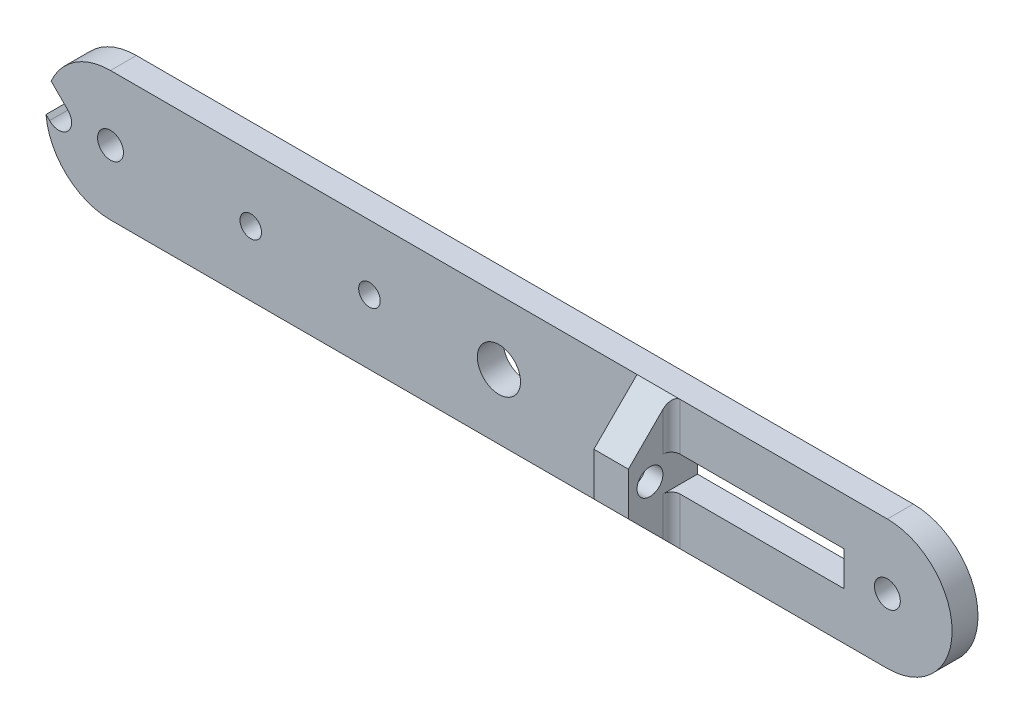
SolidWorks part; units mm, degrees
ref_plane "Plan de face" through (0, 0, 0) normal (0, 0, 1) x (1, 0, 0)
ref_plane "Plan de dessus" through (0, 0, 0) normal (0, 1, 0) x (1, 0, 0)
ref_plane "Plan de droite" through (0, 0, 0) normal (1, 0, 0) x (0, 0, -1)
sketch "Esquisse1" plane through (0, 0, 0) normal (0, 0, 1) x (1, 0, 0)
  line L0 (-74.3787, 0) -> (69.7437, 0) construction
  line L1 (0, 0) -> (0, 19.0596) construction
  line L2 (90, -15) -> (-90, -15)
  line L3 (90, 15) -> (-90, 15)
  line L5 (40, -4) -> (80, -4)
  line L6 (40, -4) -> (40, 4)
  line L7 (40, 4) -> (80, 4)
  line L8 (80, -4) -> (80, 4)
  line L9 (40, -4) -> (80, 4) construction
  line L10 (40, 4) -> (80, -4) construction
  arc A0 (90, -15) -> (90, 15) centre (90, 0) ccw
  circle A1 centre (90, 0) radius 3
  circle A2 centre (-90, 0) radius 3
  arc A3 (-90, -15) -> (-90, 15) centre (-90, 0) cw
  circle A4 centre (0, 0) radius 5
  circle A5 centre (-57.5, 0) radius 2.5
  circle A6 centre (-30, 0) radius 2.5
  point P4 (60, 0)
  point P17 (0, -15)
  point P20 (0, 15)
  dimension "D1" = 30
  dimension "D3" = 6
  dimension "D7" = 10
  dimension "D8" = 5
  dimension "D9" = 5
  dimension "D2" = 90
  dimension "D4" = 8
  dimension "D5" = 40
  dimension "D6" = 60
  dimension "D10" = 30
  dimension "D11" = 30
extrude "Boss.-Extru.1" add sketch "Esquisse1" along normal blind 6
sketch "Esquisse2" plane through (40, 0, 0) normal (1, 0, 0) x (0, 0, -1)
  line L0 (0, -4) -> (-6, 4) construction
  line L1 (-6, 4) -> (-6, 0) construction
  line L2 (-6, 4) -> (-6, -4) construction
  line L3 (-6, 0) -> (-15.5036, 0) construction
  line L4 (-6, 15) -> (-6, -15) construction
  line L6 (-16, 5) -> (-16, -5)
  line L8 (-6, 5) -> (-6, -5)
  line L9 (-16, 5) -> (-6, -5) construction
  line L10 (-16, -5) -> (-6, 5) construction
  line L11 (-6, -15) -> (-16, -5)
  line L12 (-6, -15) -> (-6, -5)
  line L13 (-6, 5) -> (-6, 15)
  line L14 (-6, 15) -> (-16, 5)
  circle A0 centre (-11, 0) radius 3
  point P7 (-11, 0)
  dimension "D3" = 6
  dimension "D1" = 10
  dimension "D2" = 10
extrude "Boss.-Extru.2" add sketch "Esquisse2" against normal blind 8
fillet "Congé2" radius 2 2 edges
sketch "Esquisse3" plane through (32, 0, 0) normal (-1, 0, 0) x (0, 0, 1)
  line L0 (11, 0) -> (11, 4) construction
  line L1 (11, 0) -> (14.4641, 2) construction
  line L2 (11, 0) -> (14.4641, -2) construction
  line L3 (11, 4) -> (14.4641, 2)
  line L4 (14.4641, 2) -> (14.4641, -2)
  line L5 (14.4641, -2) -> (11, -4)
  line L6 (7.5359, 2) -> (7.5359, -2)
  line L7 (11, 4) -> (7.5359, 2)
  line L8 (7.5359, -2) -> (11, -4)
  dimension "D2" = 60
  dimension "D3" = 60
extrude "Enlèv. mat.-Extru.1" cut sketch "Esquisse3" against normal blind 4
sketch "Esquisse4" plane through (0, 0, 6) normal (0, 0, 1) x (1, 0, 0)
  line L0 (-90, 0) -> (-105, 0) construction
  line L1 (-105, 0) -> (-102, 0) construction
  line L2 (-102, 0) -> (-104.1213, -2.1213) construction
  line L3 (-104.1213, -2.1213) -> (-99.8787, 2.1213)
  line L4 (-104.1213, -2.1213) -> (-99.8787, 2.1213)
  line L5 (-104.1213, -2.1213) -> (-108.504, 2.2614)
  line L6 (-99.8787, 2.1213) -> (-104.2614, 6.504)
  line L7 (-108.504, 2.2614) -> (-104.2614, 6.504)
  arc A0 (-90, 15) -> (-90, -15) centre (-90, 0) ccw construction
  circle A1 centre (-102, 0) radius 3
  arc M9 (-90, 15) -> (-90, -15) centre (-90, 0) ccw
  dimension "D1" = 3
  dimension "D2" = 45
extrude "Enlèv. mat.-Extru.4" cut sketch "Esquisse4" against normal blind 10 contours L3 A1 | A1 L6 M9 | A1 L5 M9 | L3 A1 region at (-102.9003, 0.9003, 6) region at (-101.0997, -0.9003, 6) region at (-104.7977, -1.1965, 6) region at (-103.2777, 3.6386, 6)
